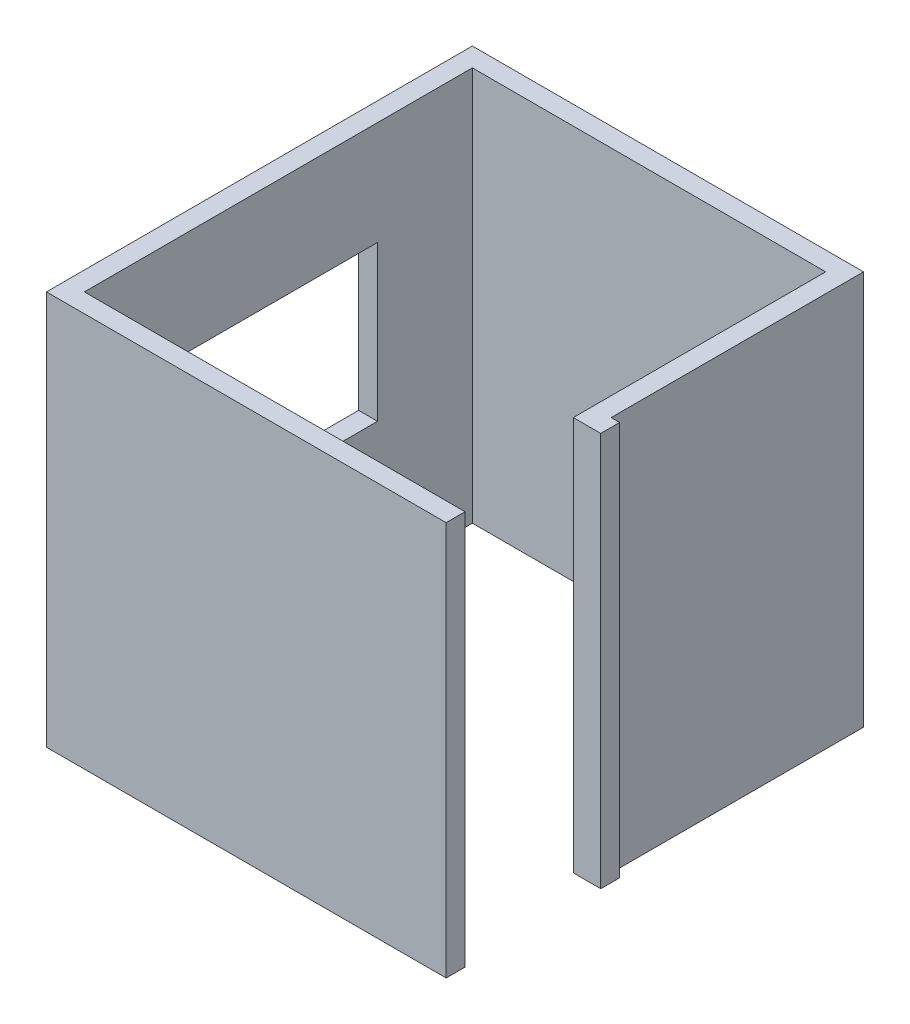
SolidWorks part; units mm, degrees
ref_plane "Спереди" through (0, 0, 0) normal (0, 0, 1) x (1, 0, 0)
ref_plane "Сверху" through (0, 0, 0) normal (0, 1, 0) x (1, 0, 0)
ref_plane "Справа" through (0, 0, 0) normal (1, 0, 0) x (0, 0, -1)
sketch "Эскиз1" plane through (0, 0, 0) normal (0, 1, 0) x (1, 0, 0)
  line L0 (0, 0) -> (0, 2460)
  line L1 (0, 2460) -> (2240, 2460)
  line L2 (2240, 2460) -> (2240, 860)
  line L3 (2240, 860) -> (2413.9408, 860)
  line L4 (0, 0) -> (2413.9408, 0)
  point P4 (2462.4135, 0)
  point P8 (0, 0)
  point P9 (0, 0)
  point P10 (0, 0)
  point P11 (2413.9408, 755.7736)
  point P12 (0, 0)
  point P13 (0, 0)
  point P14 (2459.8935, 860)
  point P15 (2454.4442, 860)
  point P16 (0, 0)
  point P17 (0, 0)
  point P18 (2367.2545, 860)
  point P19 (2413.9408, 860)
  point P20 (0, 0)
  dimension "D1" = 1600
  dimension "D2" = 2460
  dimension "D3" = 2240
extrude "Вытянуть-Тонкостенный1" add sketch "Эскиз1" along normal blind 2500 thin thin type one direction wall 120
sketch "Эскиз2" plane through (-120, 0, 0) normal (-1, 0, 0) x (0, 0, 1)
  line L1 (-1859, 1842.1461) -> (-489, 1842.1461)
  line L2 (-1859, 1842.1461) -> (-1859, 860)
  line L3 (-1859, 860) -> (-489, 860)
  line L4 (-489, 1842.1461) -> (-489, 860)
  point P4 (0, 0)
extrude "Вырез-Вытянуть1" cut sketch "Эскиз2" against normal up to next
